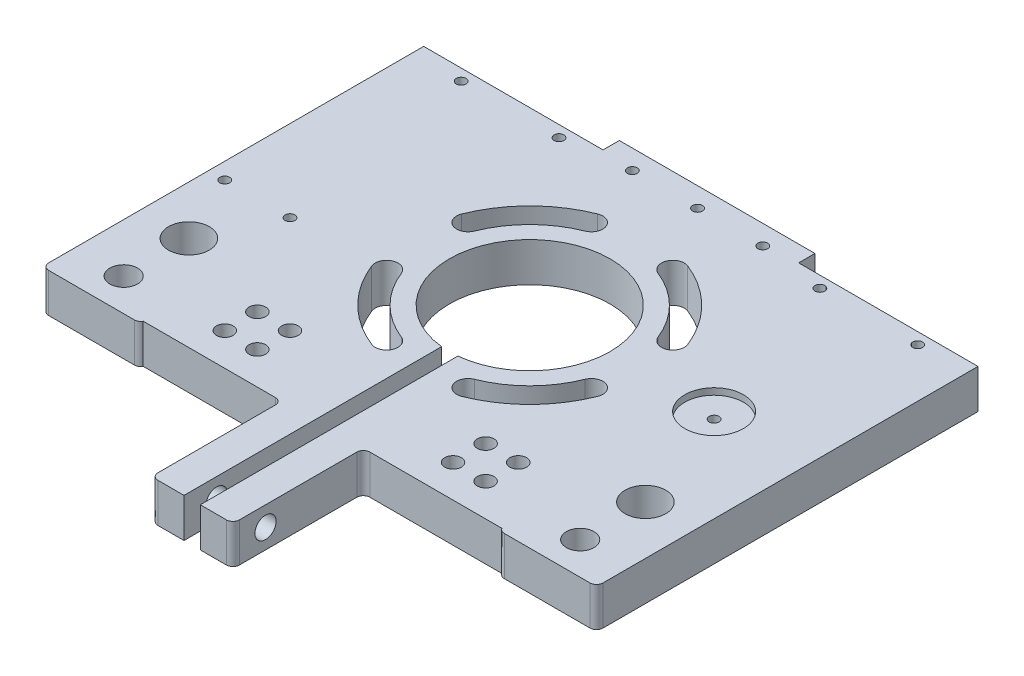
SolidWorks part; units mm, degrees
ref_plane "Front Plane" through (0, 0, 0) normal (0, 0, 1) x (1, 0, 0)
ref_plane "Top Plane" through (0, 0, 0) normal (0, 1, 0) x (1, 0, 0)
ref_plane "Right Plane" through (0, 0, 0) normal (1, 0, 0) x (0, 0, -1)
sketch "Sketch1" plane through (0, 0, 0) normal (0, 1, 0) x (1, 0, 0)
  line L0 (55, 122) -> (55, 117)
  line L1 (55, 117) -> (0, 117)
  line L2 (115, 117) -> (170, 117)
  line L3 (115, 122) -> (115, 117)
  line L4 (0, 113.5) -> (170, 113.5) construction
  line L5 (15, 10) -> (15, 30) construction
  line L6 (0, 51) -> (31.2815, 51) construction
  line L7 (15, 51) -> (15, 43.2851) construction
  line L8 (55, 21) -> (55, 11) construction
  line L9 (45, 21) -> (55, 21) construction
  line L10 (45, 21) -> (45, 11) construction
  line L11 (45, 11) -> (55, 11) construction
  line L25 (85, 122) -> (85, 0.4842) construction
  line L26 (55, 122) -> (115, 122)
  line L27 (0, 117) -> (0, 0)
  line L28 (0, 0) -> (30, 0)
  line L29 (170, 117) -> (170, 0)
  line L30 (0, 64.5229) -> (170, 64.5229) construction
  line L31 (30, 0) -> (30, 1)
  line L32 (30, 1) -> (72.5, 1)
  line L33 (72.5, 1) -> (72.5, -39)
  line L34 (72.5, -39) -> (82.5, -39)
  line L35 (82.5, -39) -> (82.5, 40)
  line L36 (0, 20) -> (170, 20) construction
  line L37 (87.5, -39) -> (87.5, 40)
  line L38 (97.5, 1) -> (97.5, -39)
  line L39 (97.5, -39) -> (87.5, -39)
  line L40 (140, 1) -> (97.5, 1)
  line L41 (140, 0) -> (140, 1)
  line L42 (140, 0) -> (170, 0)
  line L43 (155, 0) -> (155, 20) construction
  line L44 (0, 116) -> (170, 116) construction
  circle A0 centre (65, 116) radius 1.5
  circle A1 centre (105, 116) radius 1.5
  circle A2 centre (45, 113.5) radius 1.5
  circle A3 centre (15, 113.5) radius 1.5
  circle A4 centre (155, 113.5) radius 1.5
  circle A5 centre (125, 113.5) radius 1.5
  circle A6 centre (15, 30) radius 6.25
  circle A7 centre (155, 30) radius 6.25
  circle A8 centre (5, 51) radius 1.5
  circle A9 centre (25, 51) radius 1.5
  circle A10 centre (45, 11) radius 2.55
  circle A11 centre (55, 11) radius 2.55
  circle A12 centre (45, 21) radius 2.55
  circle A13 centre (55, 21) radius 2.55
  circle A14 centre (125, 11) radius 2.55
  circle A15 centre (125, 21) radius 2.55
  circle A16 centre (115, 21) radius 2.55
  circle A17 centre (115, 11) radius 2.55
  arc A26 (87.5, 40) -> (82.5, 40) centre (85, 64.5229) ccw
  circle A27 centre (155, 10) radius 4.25
  circle A28 centre (15, 10) radius 4.25
  arc A29 (53.5963, 77.0229) -> (72.5, 95.9266) centre (85, 64.5229) cw construction
  arc A30 (71.2056, 99.1784) -> (50.3445, 78.3173) centre (85, 64.5229) ccw
  arc A31 (73.7944, 92.6747) -> (56.8482, 75.7285) centre (85, 64.5229) ccw
  arc A32 (73.7944, 92.6747) -> (71.2056, 99.1784) centre (72.5, 95.9266) ccw
  arc A33 (50.3445, 78.3173) -> (56.8482, 75.7285) centre (53.5963, 77.0229) ccw
  arc A34 (116.4037, 77.0229) -> (97.5, 95.9266) centre (85, 64.5229) ccw construction
  arc A35 (98.7944, 99.1784) -> (119.6555, 78.3173) centre (85, 64.5229) cw
  arc A36 (96.2056, 92.6747) -> (113.1518, 75.7285) centre (85, 64.5229) cw
  arc A37 (96.2056, 92.6747) -> (98.7944, 99.1784) centre (97.5, 95.9266) cw
  arc A38 (119.6555, 78.3173) -> (113.1518, 75.7285) centre (116.4037, 77.0229) cw
  arc A39 (53.5963, 52.0229) -> (72.5, 33.1192) centre (85, 64.5229) ccw construction
  arc A40 (71.2056, 29.8674) -> (50.3445, 50.7285) centre (85, 64.5229) cw
  arc A41 (73.7944, 36.3711) -> (56.8482, 53.3173) centre (85, 64.5229) cw
  arc A42 (73.7944, 36.3711) -> (71.2056, 29.8674) centre (72.5, 33.1192) cw
  arc A43 (50.3445, 50.7285) -> (56.8482, 53.3173) centre (53.5963, 52.0229) cw
  arc A44 (116.4037, 52.0229) -> (97.5, 33.1192) centre (85, 64.5229) cw construction
  arc A45 (98.7944, 29.8674) -> (119.6555, 50.7285) centre (85, 64.5229) ccw
  arc A46 (96.2056, 36.3711) -> (113.1518, 53.3173) centre (85, 64.5229) ccw
  arc A47 (96.2056, 36.3711) -> (98.7944, 29.8674) centre (97.5, 33.1192) ccw
  arc A48 (119.6555, 50.7285) -> (113.1518, 53.3173) centre (116.4037, 52.0229) ccw
  circle A49 centre (85, 116) radius 1.5
  point P81 (85, 64.5229)
  point P84 (155, 10)
  point P108 (61.0998, 88.4231)
  point P115 (108.9002, 88.4231)
  point P122 (61.0998, 40.6227)
  point P129 (108.9002, 40.6227)
  point P134 (85, 116)
  dimension "D4" = 5
  dimension "D9" = 12.5
  dimension "D11" = 1
  dimension "D12" = 21
  dimension "D13" = 20
  dimension "D14" = 5.1
  dimension "D15" = 10
  dimension "D17" = 10
  dimension "D25" = 49.3
  dimension "D31" = 8.5
  dimension "D35" = 7
  dimension "D37" = 18
  dimension "D38" = 18
  dimension "D39" = 3
  dimension "D1" = 60
  dimension "D5" = 20
  dimension "D6" = 20
  dimension "D7" = 30
  dimension "D8" = 3.5
  dimension "D10" = 20
  dimension "D16" = 10
  dimension "D18" = 60
  dimension "D19" = 33.8
  dimension "D23" = 122
  dimension "D24" = 170
  dimension "D26" = 30
  dimension "D27" = 20
  dimension "D28" = 5
  dimension "D29" = 40
  dimension "D32" = 20
  dimension "D33" = 6
  dimension "D34" = 10
extrude "Boss-Extrude1" add sketch "Sketch1" along normal blind 12
sketch "Sketch2" plane through (0, 12, 0) normal (0, 1, 0) x (1, 0, 0)
  line L0 (85, 64.5229) -> (0, 64.5229) construction
  line L1 (115, 122) -> (55, 122) construction
  line L2 (170, 0) -> (170, 117) construction
  line L4 (85, -95.05) -> (85, 122) construction
  line L7 (85, 64.5229) -> (170, 64.5229) construction
  circle A1 centre (141.55, 64.5229) radius 9
  arc A3 (87.5, 40) -> (82.5, 40) centre (85, 64.5229) ccw construction
  dimension "D2" = 18
  dimension "D4" = 72.2
extrude "Cut-Extrude1" cut sketch "Sketch2" against normal blind 2
sketch "Sketch3" plane through (0, 10, 0) normal (0, 1, 0) x (1, 0, 0)
  circle A1 centre (141.55, 64.5229) radius 1.5
  dimension "D1" = 3
extrude "Cut-Extrude2" cut sketch "Sketch3" against normal through all
sketch "Sketch4" plane through (72.5, 0, 0) normal (-1, 0, 0) x (0, 0, 1)
  line L0 (29, 12.2641) -> (29, 0.2641) construction
  line L3 (39, 6) -> (-1, 6) construction
  line L5 (-1, 12) -> (-1, 0) construction
  line L7 (39, 12) -> (39, 0) construction
  circle A0 centre (29, 6) radius 3.25
  point P23 (29, 6)
  dimension "D1" = 6.5
  dimension "D2" = 10
extrude "Cut-Extrude3" cut sketch "Sketch4" along direction (-1, 0, 0) on the side against the normal up to surface (25 mm away) up to face at (97.5, 6, 19)
fillet "Fillet1" radius 2 8 edges at (170, 6, 0) (140, 6, 0) (72.5, 6, -1) (97.5, 6, -1) (97.5, 6, 39) (72.5, 6, 39) (0, 6, 0) (30, 6, 0)
